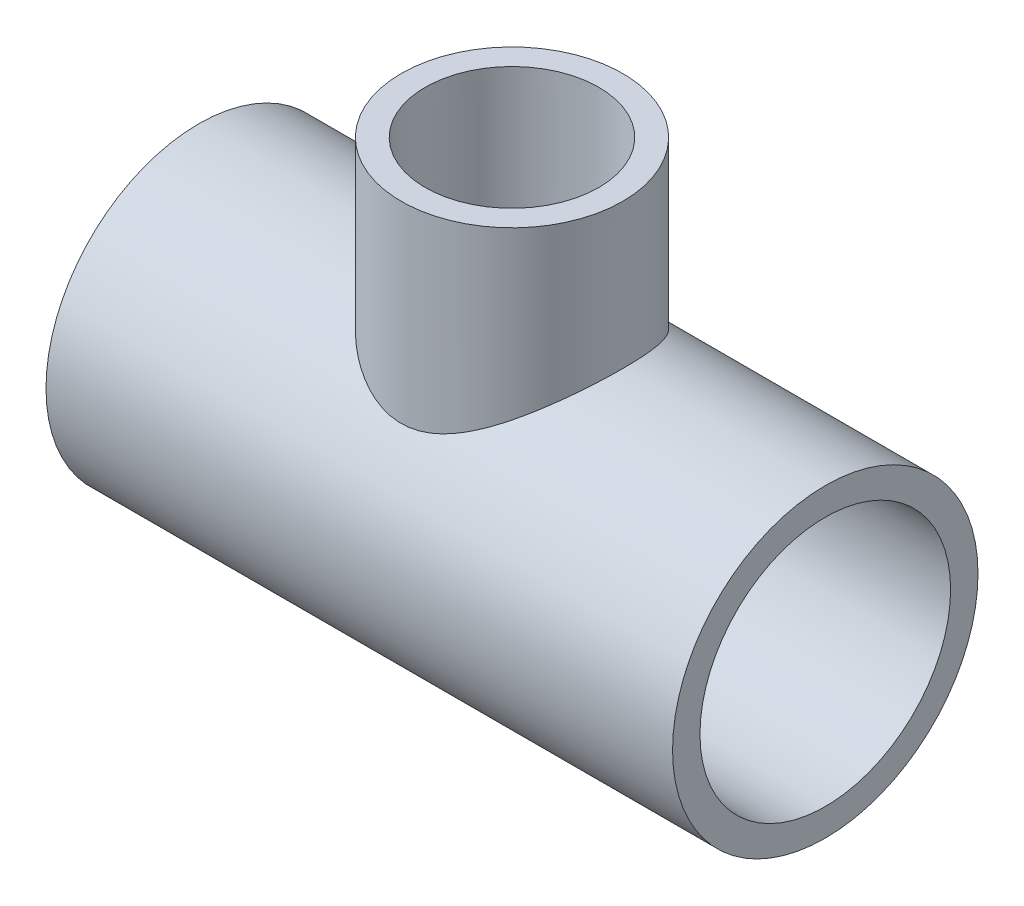
SolidWorks part; units mm, degrees
ref_plane "Front Plane" through (0, 0, 0) normal (0, 0, 1) x (1, 0, 0)
ref_plane "Top Plane" through (0, 0, 0) normal (0, 1, 0) x (1, 0, 0)
ref_plane "Right Plane" through (0, 0, 0) normal (1, 0, 0) x (0, 0, -1)
sketch "Sketch0" plane through (0, 0, 0) normal (0, 0, 1) x (1, 0, 0)
  line L0 (-60.706, 0) -> (0, 0) construction
  line L1 (0, 0) -> (0, 57.658) construction
  line L2 (-25.654, 0) -> (0, 0) construction
  line L3 (0, 0) -> (0, 25.908) construction
  line L4 (-60.706, 29.591) -> (-60.706, -29.591) construction
  line L5 (-25.654, 24.0538) -> (-60.706, 24.2824) construction
  line L6 (-25.654, 24.0538) -> (-25.654, -24.0538) construction
  line L7 (-25.654, -24.0538) -> (-60.706, -24.2824) construction
  line L8 (-60.706, 24.2824) -> (-60.706, -24.2824) construction
  line L9 (-21.463, 57.658) -> (21.463, 57.658) construction
  line L10 (-16.8275, 57.658) -> (16.8275, 57.658) construction
  line L11 (16.8275, 57.658) -> (16.637, 25.908) construction
  line L12 (16.637, 25.908) -> (-16.637, 25.908) construction
  line L13 (-16.637, 25.908) -> (-16.8275, 57.658) construction
  line L14 (-25.654, 19.05) -> (-25.654, -19.05) construction
  line L15 (-60.706, 0) -> (-25.654, 0) construction
  line L16 (0, 57.658) -> (0, 25.908) construction
  line L17 (0, 0) -> (25.654, 0) construction
  line L18 (-12.1539, 25.908) -> (12.1539, 25.908) construction
  line L19 (25.654, 0) -> (60.706, 0) construction
  dimension "D1" = 35.052
  dimension "H" = 60.706
  dimension "G" = 25.654
  dimension "M" = 59.182
  dimension "OD A" = 48.5648
  dimension "OD B" = 48.1076
  dimension "ID" = 38.1
  dimension "H3" = 57.658
  dimension "G3" = 25.908
  dimension "M3" = 42.926
  dimension "D2" = 31.75
  dimension "OD A3" = 33.655
  dimension "OD B3" = 33.274
  dimension "ID3" = 24.3078
sketch "Sketch1" plane through (0, 0, 0) normal (0, 0, 1) x (1, 0, 0)
  line L0 (-60.706, 0) -> (0, 0) construction
  line L1 (-60.706, 0) -> (0, 0) construction
  line L2 (0, 0) -> (0, -29.591) construction
  line L3 (-60.706, -29.591) -> (-25.654, -29.591)
  line L4 (-60.706, -29.591) -> (-60.706, -24.2824)
  line L5 (-60.706, -24.2824) -> (-25.654, -24.0538)
  line L6 (-25.654, -29.591) -> (-25.654, -24.0538)
  line L7 (-25.654, -29.591) -> (0, -29.591) construction
  line L8 (60.706, -24.2824) -> (25.654, -24.0538)
  line L9 (60.706, -29.591) -> (60.706, -24.2824)
  line L10 (25.654, -29.591) -> (25.654, -24.0538)
  line L11 (60.706, -29.591) -> (25.654, -29.591)
revolve "Revolve1" add sketch "Sketch1" angle 360 about L1
sketch "Sketch2" plane through (0, 0, 0) normal (0, 0, 1) x (1, 0, 0)
  line L0 (16.8275, 57.658) -> (16.637, 25.908)
  line L1 (16.637, 25.908) -> (21.463, 25.908)
  line L2 (21.463, 25.908) -> (21.463, 57.658)
  line L3 (21.463, 57.658) -> (16.8275, 57.658)
  line L4 (0, 0) -> (0, 57.658) construction
  line L5 (0, 0) -> (0, 57.658) construction
revolve "Revolve2" add sketch "Sketch2" angle 360 about L5
sketch "Sketch3" plane through (-25.654, 0, 0) normal (1, 0, 0) x (0, 0, -1)
  circle A0 centre (0, 0) radius 19.05
  circle A1 centre (0, 0) radius 29.591
sketch "Sketch4" plane through (-25.654, 0, 0) normal (1, 0, 0) x (0, 0, -1)
  circle A0 centre (0, 0) radius 29.591 construction
  circle A1 centre (0, 0) radius 29.591
extrude "Boss-Extrude1" add sketch "Sketch4" along normal up to vertex (51.308 mm away) up to point (25.654, 0, 0)
sketch "Sketch5" plane through (0, 25.908, 0) normal (0, -1, 0) x (1, 0, 0)
  circle A0 centre (0, 0) radius 21.463 construction
  circle A1 centre (0, 0) radius 21.463
extrude "Boss-Extrude2" add sketch "Sketch5" along normal up to vertex (25.908 mm away) up to point (0, 0, 0)
sketch "Sketch6" plane through (0, 0, 0) normal (0, 0, 1) x (1, 0, 0)
  line L0 (-60.706, -24.2824) -> (-25.654, -24.0538)
  line L1 (-25.654, -24.0538) -> (-25.654, -19.05)
  line L2 (-25.654, -19.05) -> (25.654, -19.05)
  line L3 (25.654, -24.0538) -> (25.654, 24.0538) construction
  line L4 (0, -19.05) -> (0, 0) construction
  line L5 (25.654, -24.0538) -> (25.654, -19.05)
  line L6 (60.706, -24.2824) -> (60.706, 24.2824) construction
  line L7 (60.706, -29.591) -> (60.706, 29.591) construction
  line L8 (60.706, -24.2824) -> (60.706, 0)
  line L9 (60.706, 0) -> (-60.706, 0)
  line L10 (-60.706, 0) -> (-60.706, -24.2824)
  line L11 (60.706, -24.2824) -> (25.654, -24.0538)
revolve "Cut-Revolve1" cut sketch "Sketch6" angle 360 about L9
sketch "Sketch7" plane through (0, 0, 0) normal (0, 0, 1) x (1, 0, 0)
  line L0 (16.8275, 57.658) -> (16.637, 25.908)
  line L1 (16.637, 25.908) -> (12.1539, 25.908)
  line L2 (12.1539, 25.908) -> (12.1539, 0)
  line L3 (0, 0) -> (25.654, 0) construction
  line L4 (12.1539, 0) -> (0, 0)
  line L5 (0, 0) -> (0, 57.658)
  line L6 (-21.463, 57.658) -> (21.463, 57.658) construction
  line L7 (0, 57.658) -> (16.8275, 57.658)
revolve "Cut-Revolve2" cut sketch "Sketch7" angle 360 about L5
other "CPoint1" parameters "Diameter"=38.1, "StubLength"=38.1
ref_axis "Axis1" through (-35.654, 0, 0) along (1, 0, 0)
other "CPoint2" parameters "Diameter"=38.1, "StubLength"=38.1
ref_axis "Axis2" through (35.654, 0, 0) along (-1, 0, 0)
other "CPoint3" parameters "Diameter"=25.4, "StubLength"=38.1
ref_axis "Axis3" through (0, 35.908, 0) along (0, -1, 0)
other "RPoint1"
